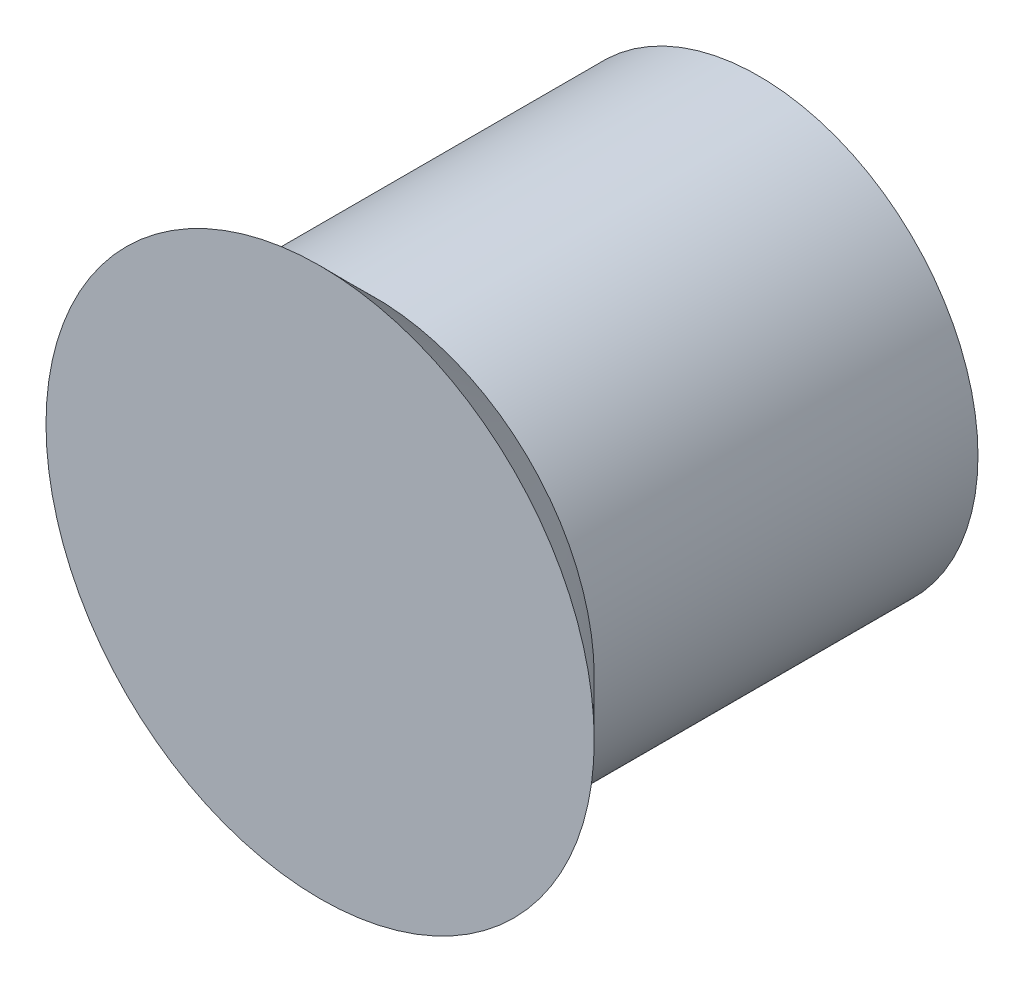
SolidWorks part; units mm, degrees
ref_plane "Ön Düzlem" through (0, 0, 0) normal (0, 0, 1) x (1, 0, 0)
ref_plane "Üst Düzlem" through (0, 0, 0) normal (0, 1, 0) x (1, 0, 0)
ref_plane "Sağ Düzlem" through (0, 0, 0) normal (1, 0, 0) x (0, 0, -1)
sketch "Çizim1" plane through (0, 0, 0) normal (0, 0, 1) x (1, 0, 0)
  circle A0 centre (0, 0) radius 4
  dimension "D1" = 8
extrude "Yükseklik-Ekstrüzyon1" add sketch "Çizim1" along normal blind 7
sketch "Çizim2" plane through (0, 0, 7) normal (0, 0, 1) x (1, 0, 0)
  circle A0 centre (0, 0) radius 4
extrude "Yükseklik-Ekstrüzyon2" add sketch "Çizim2" along normal blind 1 draft 45 draft outward yes
